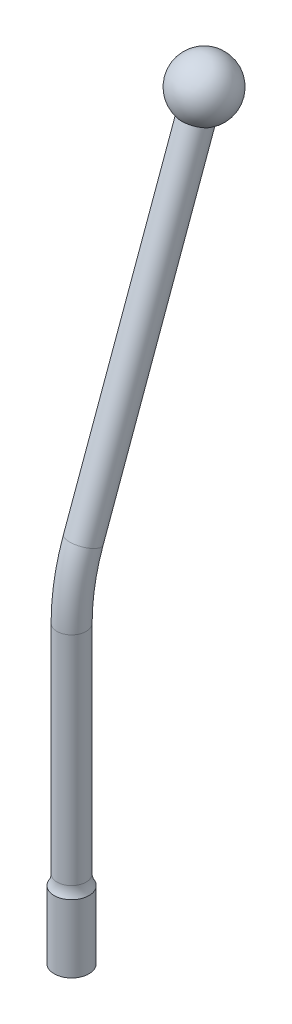
SolidWorks part; units mm, degrees
ref_plane "前视基准面" through (0, 0, 0) normal (0, 0, 1) x (1, 0, 0)
ref_plane "上视基准面" through (0, 0, 0) normal (0, 1, 0) x (1, 0, 0)
ref_plane "右视基准面" through (0, 0, 0) normal (1, 0, 0) x (0, 0, -1)
other "Configuration Table"
sketch "草图1" plane through (0, 0, 0) normal (0, 1, 0) x (1, 0, 0)
  circle A0 centre (0, 0) radius 0.9
  dimension "D1" = 1.8
extrude "凸台-拉伸1" add sketch "草图1" along normal blind 3.5
sketch "草图2" plane through (0, 0, 0) normal (1, 0, 0) x (0, 0, -1)
  line L0 (6.8404, 35.7939) -> (0.6031, 18.6569)
  line L1 (0, 15.2367) -> (0, 3)
  line L3 (0.9, 3.5) -> (-0.9, 3.5) construction
  arc A0 (0, 15.2367) -> (0.6031, 18.6569) centre (10, 15.2367) cw
  point P21 (0, 17)
  dimension "D6" = 10
  dimension "D1" = 0.5
  dimension "D2" = 160
  dimension "D3" = 14
  dimension "D4" = 20
  dimension "D5" = 90
ref_plane "基准面1" through (0, 3, 0) normal (0, -1, 0) x (-1, 0, 0)
sweep "扫描1" add path "草图2" circular profile diameter 1.5 parameters "D3"=1.5
sketch "草图20" plane through (0, 33.8052, -12.3041) normal (0, 0.9397, -0.342) x (1, 0, 0)
  line L0 (0, -5.8143) -> (-1.5, -5.8143) construction
  circle A0 centre (0, -5.8143) radius 1.5
  circle A1 centre (0, -5.8143) radius 0.75 construction
  dimension "D1" = 3
revolve "旋转7" add sketch "草图20" angle 360 about L0 region at (0, 35.2953, -8.2101)
fillet "圆角2" radius 1 1 edges at (0, 3.5, 0.75)
